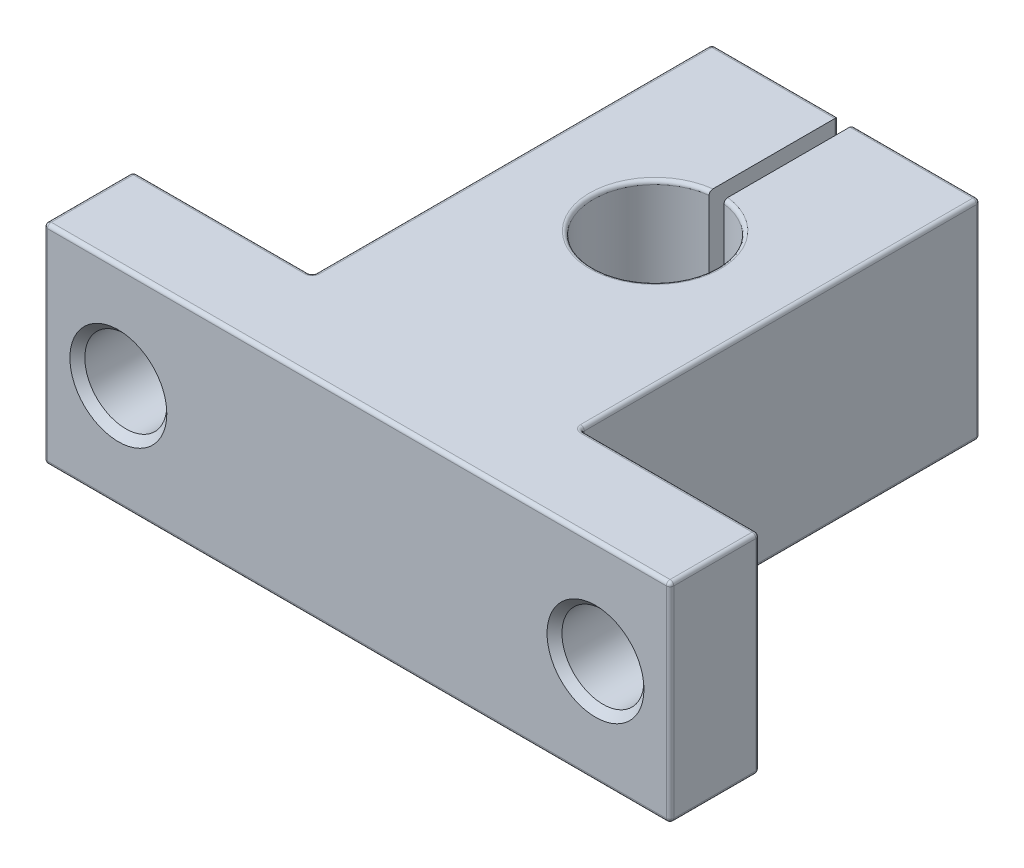
SolidWorks part; units mm, degrees
ref_plane "Front Plane" through (0, 0, 0) normal (0, 0, 1) x (1, 0, 0)
ref_plane "Top Plane" through (0, 0, 0) normal (0, 1, 0) x (1, 0, 0)
ref_plane "Right Plane" through (0, 0, 0) normal (1, 0, 0) x (0, 0, -1)
sketch "Sketch1" plane through (0, 0, 0) normal (0, 1, 0) x (1, 0, 0)
  line L1 (-21, 0) -> (21, 0)
  line L2 (21, 0) -> (21, 6)
  line L3 (-9, 32.8) -> (9, 32.8)
  line L4 (0, 32.8) -> (0, 0)
  line L5 (9, 32.8) -> (9, 6)
  line L6 (9, 6) -> (21, 6)
  line L7 (-9, 32.8) -> (-9, 6)
  line L8 (-21, 0) -> (-21, 6)
  line L9 (-9, 6) -> (-21, 6)
  line L10 (-0.5, 23.8) -> (0.5, 23.8)
  line L11 (-0.5, 23.8) -> (-0.5, 32.8)
  line L12 (-0.5, 32.8) -> (0.5, 32.8)
  line L13 (0.5, 23.8) -> (0.5, 32.8)
  line L14 (-0.5, 23.8) -> (0.5, 32.8) construction
  line L15 (-0.5, 32.8) -> (0.5, 23.8) construction
  circle A0 centre (0, 20) radius 4.15
  point P13 (0, 28.3)
  dimension "D2" = 8.3
  dimension "D6" = 20
  dimension "D1" = 21
  dimension "D3" = 6
  dimension "D4" = 32.8
  dimension "D5" = 9
  dimension "D7" = 9
  dimension "D8" = 1
extrude "Boss-Extrude1" add sketch "Sketch1" along normal blind 7 and the other way blind 7 contours A0 L11 L3 L7 L9 L8 L1 L4 | A0 L4 L1 L2 L6 L5 L3 L13 region at (-7.0266, 0, -13.0814) region at (7.0266, 0, -13.0814)
sketch "Sketch2" plane through (0, 0, 0) normal (0, 0, 1) x (1, 0, 0)
  line L0 (0, 7) -> (0, -7) construction
  line L1 (-21, 7) -> (21, 7) construction
  line L2 (-21, -7) -> (21, -7) construction
  line L3 (-21, 0) -> (21, 0) construction
  line L4 (-21, -7) -> (-21, 7) construction
  line L5 (21, -7) -> (21, 7) construction
  circle A0 centre (-16, 0) radius 2.75
  circle A1 centre (16, 0) radius 2.75
  dimension "D1" = 5.5
  dimension "D2" = 16
extrude "Cut-Extrude1" cut sketch "Sketch2" against normal up to next
fillet "Fillet1" radius 0.25 30 edges at (15, -7, -6) (15, 7, -6) (-9, -7, -19.4) (-9, 7, -19.4) (9, -7, -19.4) (9, 0, -6) (9, 7, -19.4) (4.75, -7, -32.8) (9, 0, -32.8) (4.75, 7, -32.8) (0.5, 0, -32.8) (-4.75, -7, -32.8) (-0.5, 0, -32.8) (-4.75, 7, -32.8) (-9, 0, -32.8) (21, 0, 0) (-21, 0, 0) (0, 7, 0) (0, -7, 0) (21, -7, -3) (-21, -7, -3) (-21, 7, -3) (21, 7, -3) (-15, -7, -6) (-21, 0, -6) (-15, 7, -6) (-9, 0, -6) (21, 0, -6) (0, -7, -15.85) (0, 7, -15.85)
chamfer "Chamfer1" distance 0.5 angle 45 4 edges at (13.25, 0, 0) (-13.25, 0, 0) (-18.75, 0, -6) (18.75, 0, -6)
